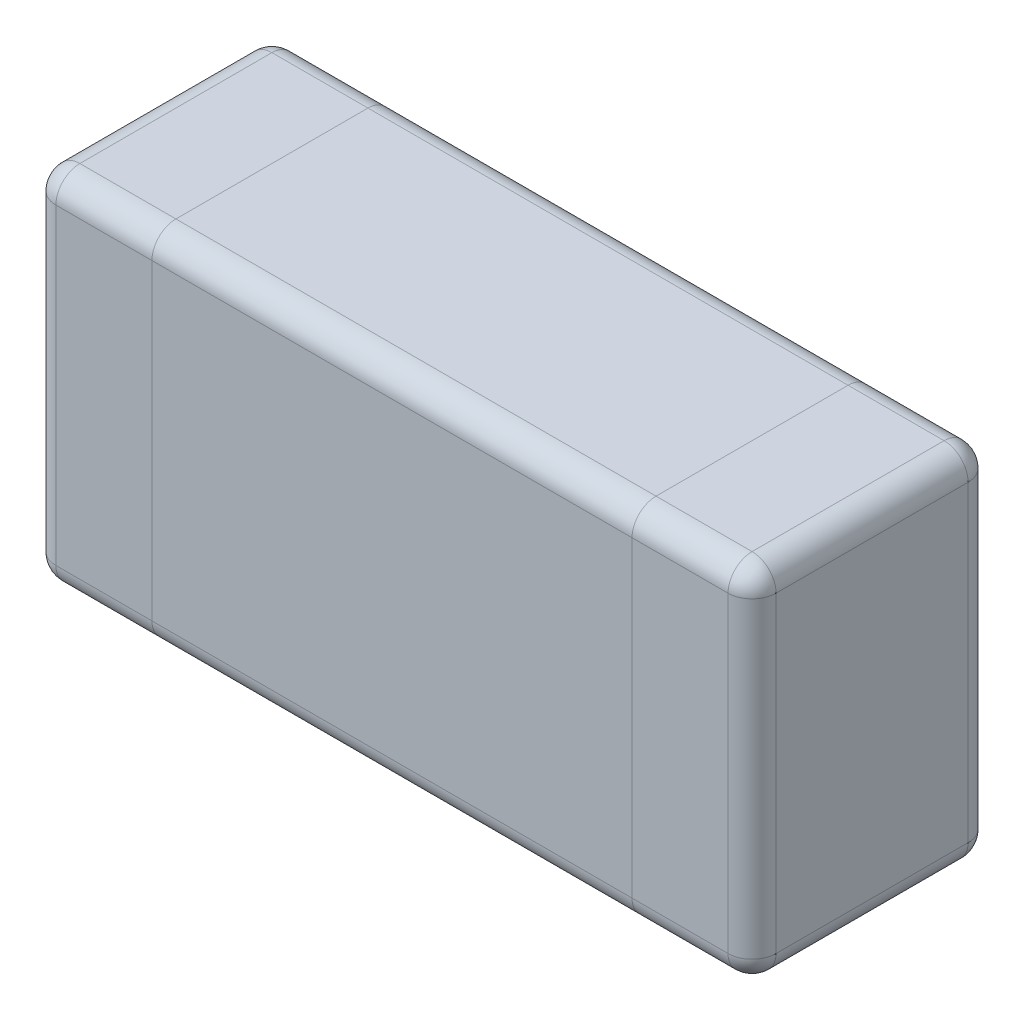
SolidWorks part; units mm, degrees
material "Ceramic Porcelain"
ref_plane "Front Plane" through (0, 0, 0) normal (0, 0, 1) x (1, 0, 0)
ref_plane "Top Plane" through (0, 0, 0) normal (0, 1, 0) x (1, 0, 0)
ref_plane "Right Plane" through (0, 0, 0) normal (1, 0, 0) x (0, 0, -1)
sketch "Sketch1" plane through (0, 0, 0) normal (0, 1, 0) x (1, 0, 0)
  line L1 (-0.2, -0.2) -> (0.2, -0.2)
  line L2 (-0.2, -0.2) -> (-0.2, 0)
  line L3 (-0.2, 0) -> (0.2, 0)
  line L4 (0.2, -0.2) -> (0.2, 0)
  dimension "D1" = 0.4
  dimension "D2" = 0.2
extrude "Boss-Extrude1" add sketch "Sketch1" along normal blind 0.15 and the other way blind 0.15
fillet "Fillet1" radius 0.02 4 edges at (0, -0.15, 0) (0, 0.15, 0) (0, -0.15, 0.2) (0, 0.15, 0.2)
sketch "Sketch2" plane through (-0.2, 0, 0) normal (-1, 0, 0) x (0, 0, 1)
  line L8 (0.02, -0.15) -> (0.18, -0.15)
  line L9 (0, 0.13) -> (0, -0.13)
  line L10 (0.18, 0.15) -> (0.02, 0.15)
  line L11 (0.2, -0.13) -> (0.2, 0.13)
  line L12 (0.02, -0.15) -> (0.18, -0.15)
  line L13 (0, 0.13) -> (0, -0.13)
  line L14 (0.18, 0.15) -> (0.02, 0.15)
  line L15 (0.2, -0.13) -> (0.2, 0.13)
  arc A8 (0, -0.13) -> (0.02, -0.15) centre (0.02, -0.13) ccw
  arc A9 (0.02, 0.15) -> (0, 0.13) centre (0.02, 0.13) ccw
  arc A10 (0.2, 0.13) -> (0.18, 0.15) centre (0.18, 0.13) ccw
  arc A11 (0.18, -0.15) -> (0.2, -0.13) centre (0.18, -0.13) ccw
  arc A12 (0, -0.13) -> (0.02, -0.15) centre (0.02, -0.13) ccw
  arc A13 (0.02, 0.15) -> (0, 0.13) centre (0.02, 0.13) ccw
  arc A14 (0.2, 0.13) -> (0.18, 0.15) centre (0.18, 0.13) ccw
  arc A15 (0.18, -0.15) -> (0.2, -0.13) centre (0.18, -0.13) ccw
  dimension "D1" = 0
extrude "Boss-Extrude2" add sketch "Sketch2" along normal blind 0.1 separate body
fillet "Fillet2" radius 0.02 8 edges at (-0.3, 0, 0.2) (-0.3, 0.1441, 0.1941) (-0.3, 0.15, 0.1) (-0.3, 0.1441, 0.0059) (-0.3, 0, 0) (-0.3, -0.1441, 0.0059) (-0.3, -0.15, 0.1) (-0.3, -0.1441, 0.1941)
mirror "Mirror1" about plane through (0, 0, 0) normal (1, 0, 0) of bodies 102
equation "\"L\"= 0.6"
equation "\"W\"= 0.3"
equation "\"H\"= 0.2"
equation "\"e\"= 0.1"
equation "\"D1@Sketch1\"=\"L\"-\"e\"*2"
equation "\"D1@Boss-Extrude1\"=\"W\"/2"
equation "\"D1@Fillet1\"=\"e\"/5"
equation "\"D1@Boss-Extrude2\"=\"e\""
equation "\"D1@Fillet2\"=\"e\"/5"
equation "\"D2@Boss-Extrude1\"=\"W\"/2"
equation "\"D2@Sketch1\"=\"H\""
